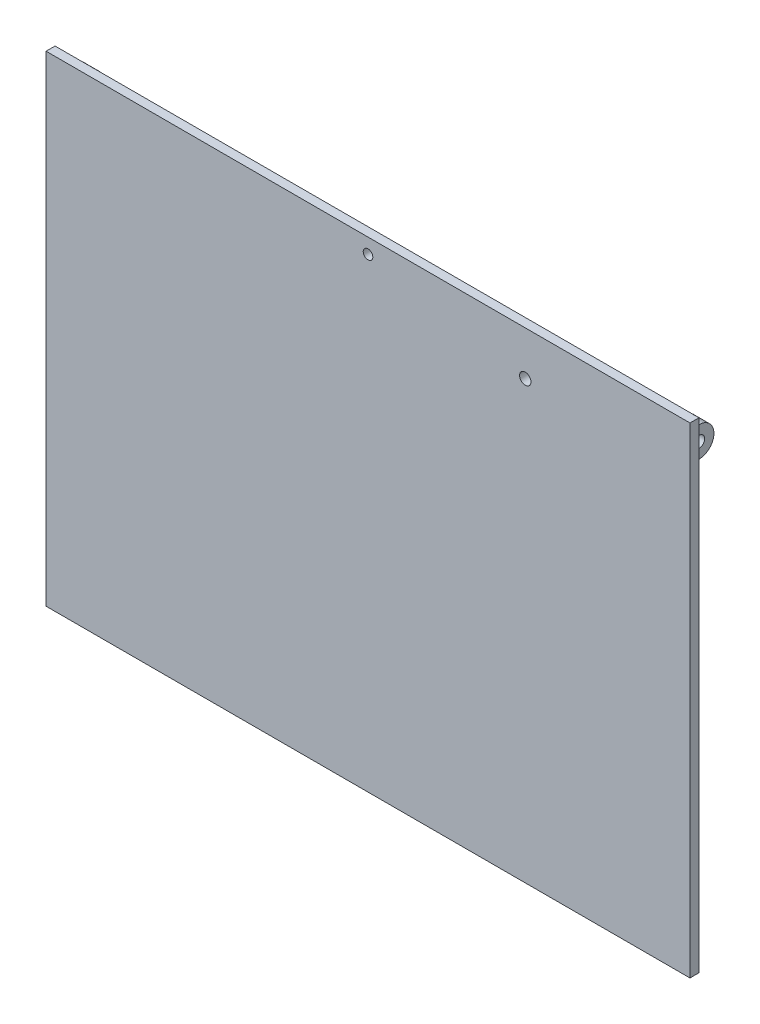
SolidWorks part; units mm, degrees
ref_plane "Płaszczyzna przednia" through (0, 0, 0) normal (0, 0, 1) x (1, 0, 0)
ref_plane "Płaszczyzna górna" through (0, 0, 0) normal (0, 1, 0) x (1, 0, 0)
ref_plane "Płaszczyzna prawa" through (0, 0, 0) normal (1, 0, 0) x (0, 0, -1)
sketch "Szkic1" plane through (0, 0, 0) normal (0, 0, 1) x (1, 0, 0)
  line L1 (0, 0) -> (215, 0)
  line L2 (0, 0) -> (0, 160.5)
  line L3 (0, 160.5) -> (215, 160.5)
  line L4 (215, 0) -> (215, 160.5)
  dimension "D1" = 215
  dimension "D2" = 160.5
extrude "Dodanie-wyciągnięcie1" add sketch "Szkic1" along normal blind 3
sketch "Szkic2" plane through (215, 0, 0) normal (1, 0, 0) x (0, 0, -1)
  line L0 (0, 0) -> (0, 160.5) construction
  line L1 (0, 155.5) -> (3, 155.5)
  line L2 (0, 155.5) -> (0, 145.5)
  line L3 (0, 145.5) -> (3, 145.5)
  arc A0 (3, 145.5) -> (3, 155.5) centre (3, 150.5) ccw
  circle A1 centre (3, 150.5) radius 1.9
  dimension "D1" = 5
  dimension "D4" = 3.8
  dimension "D2" = 10
  dimension "D3" = 5
  dimension "D5" = 3
extrude "Dodanie-wyciągnięcie2" add sketch "Szkic2" against normal blind 5 from offset 3 offset against normal yes
ref_plane "Płaszczyzna1" through (107.5, 0, 0) normal (-1, 0, 0) x (0, 0, 1)
mirror "Lustro1" about plane through (107.5, 0, 0) normal (-1, 0, 0) of "Dodanie-wyciągnięcie2"
sketch "Szkic3" plane through (0, 0, 0) normal (0, -1, 0) x (1, 0, 0)
  line L0 (0, 0) -> (215, 0) construction
  line L1 (10, 0) -> (20, 0)
  line L2 (10, 0) -> (10, -3)
  line L4 (20, 0) -> (20, -3)
  arc A0 (10, -3) -> (20, -3) centre (15, -3) ccw
  circle A1 centre (15, -3) radius 1.9
  dimension "D3" = 5
  dimension "D4" = 3.8
  dimension "D1" = 10
  dimension "D2" = 3
  dimension "D5" = 10
extrude "Dodanie-wyciągnięcie3" add sketch "Szkic3" against normal blind 5 from offset 3 offset against normal yes
mirror "Lustro2" about plane through (107.5, 0, 0) normal (-1, 0, 0) of "Dodanie-wyciągnięcie3"
chamfer "Sfazowanie1" distance 3 angle 45 4 edges at (195, 5.5, 0) (20, 5.5, 0) (5.5, 145.5, 0) (209.5, 145.5, 0)
chamfer "Sfazowanie2" distance 8 angle 10 4 edges at (16.5, 8, 0) (198.5, 8, 0) (8, 149, 0) (207, 149, 0) first distance on face at (15, 8, -4.9) first distance on face at (199.25, 8, -2.75) first distance on face at (8, 149.75, -2.75) first distance on face at (207, 150.5, -4.9)
sketch "Szkic4" plane through (0, 0, 0) normal (0, 0, -1) x (-1, 0, 0)
  line L0 (-215, 80.25) -> (0, 80.25)
  line L1 (-215, 0) -> (-215, 160.5) construction
  line L2 (0, 160.5) -> (0, 0) construction
  circle A1 centre (-107.5, 155.5) radius 1.6
extrude "Wytnij-wyciągnięcie1" cut sketch "Szkic4" against normal blind 10 contours A1 region at (107.5, 155.5, 0)
sketch "Szkic5" plane through (0, 0, 0) normal (0, 0, -1) x (-1, 0, 0)
  line L0 (-107.5, 0) -> (-107.5, 46.8676) construction
  line L1 (0, 0) -> (-215, 0) construction
  line L3 (-117.5, 3) -> (-97.5, 3)
  line L4 (-117.5, 3) -> (-117.5, 8)
  line L5 (-117.5, 8) -> (-97.5, 8)
  line L6 (-97.5, 3) -> (-97.5, 8)
  point P8 (-107.5, 8)
  dimension "D1" = 5
  dimension "D2" = 20
  dimension "D3" = 3
extrude "Dodanie-wyciągnięcie4" add sketch "Szkic5" along normal blind 38
sketch "Szkic6" plane through (0, 8, 0) normal (0, 1, 0) x (1, 0, 0)
  line L0 (215, 0) -> (0, 0) construction
  circle A0 centre (107.5, 15) radius 1.9
  dimension "D1" = 3.8
  dimension "D2" = 15
extrude "Wytnij-wyciągnięcie2" cut sketch "Szkic6" against normal blind 35
chamfer "Sfazowanie3" distance 2 angle 45 3 edges at (117.5, 5.5, 0) (107.5, 8, 0) (97.5, 5.5, 0)
sketch "Szkic7" plane through (0, 0, 0) normal (0, 0, -1) x (-1, 0, 0)
  line L0 (-215, 0) -> (-215, 160.5) construction
  line L1 (-165, 150.8) -> (-155, 150.8)
  line L2 (-165, 150.8) -> (-165, 140.8)
  line L3 (-165, 140.8) -> (-155, 140.8)
  line L4 (-155, 150.8) -> (-155, 140.8)
  line L5 (-215, 160.5) -> (0, 160.5) construction
  dimension "D1" = 10
  dimension "D2" = 50
  dimension "D3" = 9.7
extrude "Dodanie-wyciągnięcie5" add sketch "Szkic7" along normal blind 2
sketch "Szkic8" plane through (0, 0, -2) normal (0, 0, -1) x (-1, 0, 0)
  line L0 (-165, 150.8) -> (-155, 140.8) construction
  line L2 (-155, 150.8) -> (-165, 140.8) construction
  circle A0 centre (-160, 145.8) radius 1.9
  dimension "D1" = 3.8
extrude "Wytnij-wyciągnięcie3" cut sketch "Szkic8" against normal through all
